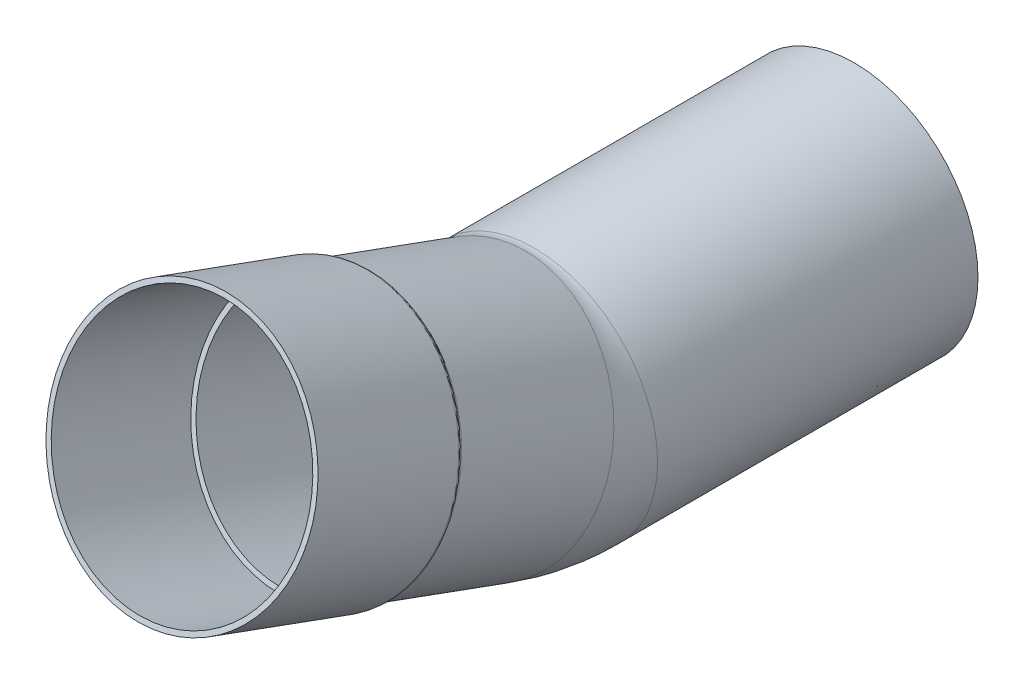
SolidWorks part; units mm, degrees
ref_plane "Plan de face" through (0, 0, 0) normal (0, 0, 1) x (1, 0, 0)
ref_plane "Plan de dessus" through (0, 0, 0) normal (0, 1, 0) x (1, 0, 0)
ref_plane "Plan de droite" through (0, 0, 0) normal (1, 0, 0) x (0, 0, -1)
sketch "Esquisse6" plane through (0, 0, 0) normal (0, 0, 1) x (1, 0, 0)
  circle A0 centre (0, 0) radius 25
sketch "Esquisse7" plane through (0, 0, 0) normal (1, 0, 0) x (0, 0, -1)
  line L0 (0, 0) -> (-64.7102, 0)
  line L1 (-74.9708, 1.8092) -> (-106.648, 13.3388)
  arc A0 (-64.7102, 0) -> (-74.9708, 1.8092) centre (-64.7102, 30) cw
  point P6 (-70, 0)
  dimension "D4" = 30
  dimension "D1" = 39
  dimension "D2" = 70
  dimension "D3" = 20
sweep "Balayage-Mince2" add profiles "Esquisse6" path "Esquisse7" parameters "D1"=1
sketch "Esquisse8" plane through (0, 35.8364, 98.4596) normal (0, 0.342, 0.9397) x (1, 0, 0)
  line L0 (-24, -23.9414) -> (24, -23.9414) construction
  line L1 (0, 0.0586) -> (0, -47.9414) construction
  circle A0 centre (0, -23.9414) radius 24 construction
  circle A1 centre (0, -23.9414) radius 24 construction
  circle A2 centre (0, -23.9414) radius 24
  point P10 (0, -23.9414)
extrude "Extru.-Mince1" add sketch "Esquisse8" along normal blind 1 separate body thin contours A2 thin type one direction wall 2
sketch "Esquisse9" plane through (0, 36.1784, 99.3993) normal (0, 0.342, 0.9397) x (1, 0, 0)
  line L0 (-24, -23.9414) -> (24, -23.9414) construction
  line L1 (0, 0.0586) -> (0, -47.9414) construction
  circle A0 centre (0, -23.9414) radius 24 construction
  circle A1 centre (0, -23.9414) radius 24 construction
  circle A2 centre (0, -23.9414) radius 26
extrude "Extru.-Mince2" add sketch "Esquisse9" along normal blind 30 thin thin type one direction reverse wall 1
fillet "Congé1" radius 1 1 edges at (25, 13.3388, 106.648)
fillet "Congé2" radius 1 1 edges at (26, 13.3388, 106.648)
